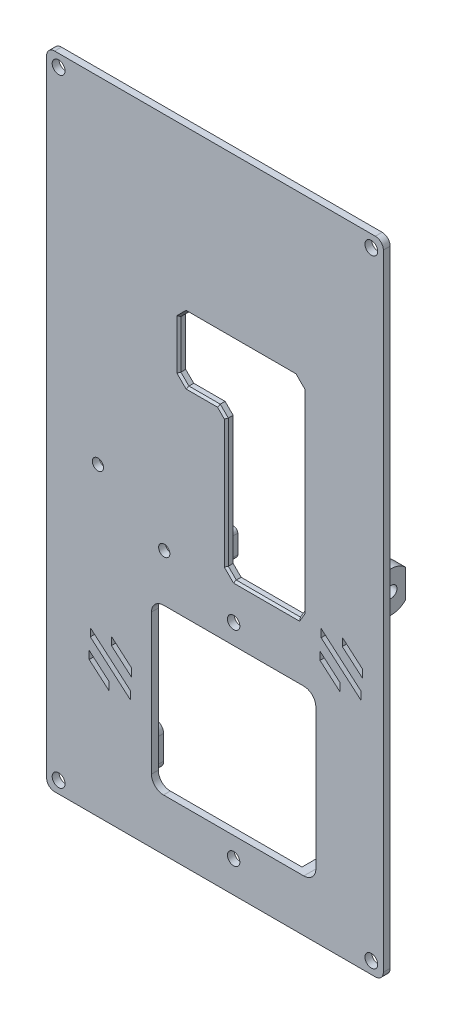
SolidWorks part; units mm, degrees
ref_plane "前视基准面" through (0, 0, 0) normal (0, 0, 1) x (1, 0, 0)
ref_plane "上视基准面" through (0, 0, 0) normal (0, 1, 0) x (1, 0, 0)
ref_plane "右视基准面" through (0, 0, 0) normal (1, 0, 0) x (0, 0, -1)
sketch "草图1" plane through (0, 0, 0) normal (0, 0, 1) x (1, 0, 0)
  line L0 (-263.3587, 1400.9403) -> (-185.3587, 1400.9403) construction
  line L17 (-203.4669, 1467.4701) -> (-189.703, 1467.4701)
  line L18 (-205.2557, 1468.5757) -> (-214.1502, 1486.3645)
  line L19 (-237.1098, 1489.3645) -> (-241.3399, 1480.9044)
  line L20 (-241.9491, 1480.1837) -> (-254.721, 1470.855)
  line L21 (-255.9007, 1470.4701) -> (-262.703, 1470.4701)
  line L22 (-266.703, 1466.4701) -> (-266.703, 1318.4701)
  line L23 (-262.703, 1314.4701) -> (-255.9007, 1314.4701)
  line L24 (-254.721, 1314.0852) -> (-241.9491, 1304.7565)
  line L25 (-241.3399, 1304.0358) -> (-237.1098, 1295.5757)
  line L26 (-235.321, 1294.4701) -> (-214.0849, 1294.4701)
  line L27 (-212.2961, 1295.5757) -> (-208.066, 1304.0358)
  line L28 (-207.4568, 1304.7565) -> (-194.6849, 1314.0852)
  line L29 (-193.5052, 1314.4701) -> (-186.703, 1314.4701)
  line L30 (-182.703, 1318.4701) -> (-182.703, 1466.4701)
  line L31 (-186.703, 1470.4701) -> (-193.5052, 1470.4701)
  line L32 (-194.6849, 1470.855) -> (-207.4568, 1480.1837)
  line L33 (-208.066, 1480.9044) -> (-212.2961, 1489.3645)
  line L34 (-214.0849, 1490.4701) -> (-235.321, 1490.4701)
  line L35 (-233.4669, 1487.4701) -> (-215.939, 1487.4701)
  line L36 (-235.2557, 1486.3645) -> (-244.1502, 1468.5757)
  line L37 (-245.939, 1467.4701) -> (-259.703, 1467.4701)
  line L38 (-263.703, 1321.4701) -> (-263.703, 1463.4701)
  line L39 (-263.703, 1321.4701) -> (-263.703, 1328.4701)
  line L40 (-259.703, 1317.4701) -> (-245.939, 1317.4701)
  line L41 (-244.1502, 1316.3645) -> (-235.2557, 1298.5757)
  line L42 (-233.4669, 1297.4701) -> (-215.939, 1297.4701)
  line L43 (-214.1502, 1298.5757) -> (-205.2557, 1316.3645)
  line L44 (-185.703, 1321.4701) -> (-185.703, 1463.4701)
  line L45 (-203.4669, 1317.4701) -> (-189.703, 1317.4701)
  circle A20 centre (-201.703, 1470.9701) radius 1.6
  circle A21 centre (-247.703, 1470.9701) radius 1.6
  circle A22 centre (-247.703, 1313.9701) radius 1.6
  circle A23 centre (-201.703, 1313.9701) radius 1.6
  arc A24 (-241.9491, 1480.1837) -> (-241.3399, 1480.9044) centre (-243.1288, 1481.7988) ccw
  arc A25 (-255.9007, 1470.4701) -> (-254.721, 1470.855) centre (-255.9007, 1472.4701) ccw
  arc A26 (-262.703, 1470.4701) -> (-266.703, 1466.4701) centre (-262.703, 1466.4701) ccw
  arc A27 (-266.703, 1318.4701) -> (-262.703, 1314.4701) centre (-262.703, 1318.4701) ccw
  arc A28 (-254.721, 1314.0852) -> (-255.9007, 1314.4701) centre (-255.9007, 1312.4701) ccw
  arc A29 (-241.3399, 1304.0358) -> (-241.9491, 1304.7565) centre (-243.1288, 1303.1414) ccw
  arc A30 (-237.1098, 1295.5757) -> (-235.321, 1294.4701) centre (-235.321, 1296.4701) ccw
  arc A31 (-214.0849, 1294.4701) -> (-212.2961, 1295.5757) centre (-214.0849, 1296.4701) ccw
  arc A32 (-207.4568, 1304.7565) -> (-208.066, 1304.0358) centre (-206.2771, 1303.1414) ccw
  arc A33 (-193.5052, 1314.4701) -> (-194.6849, 1314.0852) centre (-193.5052, 1312.4701) ccw
  arc A34 (-186.703, 1314.4701) -> (-182.703, 1318.4701) centre (-186.703, 1318.4701) ccw
  arc A35 (-182.703, 1466.4701) -> (-186.703, 1470.4701) centre (-186.703, 1466.4701) ccw
  arc A36 (-194.6849, 1470.855) -> (-193.5052, 1470.4701) centre (-193.5052, 1472.4701) ccw
  arc A37 (-208.066, 1480.9044) -> (-207.4568, 1480.1837) centre (-206.2771, 1481.7988) ccw
  arc A38 (-212.2961, 1489.3645) -> (-214.0849, 1490.4701) centre (-214.0849, 1488.4701) ccw
  arc A39 (-235.321, 1490.4701) -> (-237.1098, 1489.3645) centre (-235.321, 1488.4701) ccw
  arc A40 (-185.703, 1463.4701) -> (-189.703, 1467.4701) centre (-189.703, 1463.4701) ccw
  arc A41 (-205.2557, 1468.5757) -> (-203.4669, 1467.4701) centre (-203.4669, 1469.4701) ccw
  arc A42 (-214.1502, 1486.3645) -> (-215.939, 1487.4701) centre (-215.939, 1485.4701) ccw
  arc A43 (-233.4669, 1487.4701) -> (-235.2557, 1486.3645) centre (-233.4669, 1485.4701) ccw
  arc A44 (-245.939, 1467.4701) -> (-244.1502, 1468.5757) centre (-245.939, 1469.4701) ccw
  arc A45 (-259.703, 1467.4701) -> (-263.703, 1463.4701) centre (-259.703, 1463.4701) ccw
  arc A46 (-263.703, 1321.4701) -> (-259.703, 1317.4701) centre (-259.703, 1321.4701) ccw
  arc A47 (-244.1502, 1316.3645) -> (-245.939, 1317.4701) centre (-245.939, 1315.4701) ccw
  arc A48 (-235.2557, 1298.5757) -> (-233.4669, 1297.4701) centre (-233.4669, 1299.4701) ccw
  arc A49 (-215.939, 1297.4701) -> (-214.1502, 1298.5757) centre (-215.939, 1299.4701) ccw
  arc A50 (-203.4669, 1317.4701) -> (-205.2557, 1316.3645) centre (-203.4669, 1315.4701) ccw
  arc A51 (-189.703, 1317.4701) -> (-185.703, 1321.4701) centre (-189.703, 1321.4701) ccw
  dimension "D2" = 3.2
  dimension "D3" = 3.2
  dimension "D4" = 3.2
  dimension "D5" = 3.2
  dimension "D1" = 78
extrude "凸台-拉伸2" add sketch "草图1" along normal blind 1.7 contours L34 A39 L19 A24 L20 A25 L21 A26 L22 A27 L23 A28 L24 A29 L25 A30 L26 A31 L27 A32 L28 A33 L29 A34 L30 A35 L31 A36 L32 A37 L33 A38 A51 L45 A50 L43 A49 L42 A48 L41 A47 L40 A46 L38 A45 L37 A44 L36 A43
sketch "草图2" plane through (0, 0, 0) normal (0, 0, -1) x (-1, 0, 0)
  line L0 (203.4669, 1467.4701) -> (189.703, 1467.4701) construction
  line L1 (205.2557, 1468.5757) -> (214.1502, 1486.3645) construction
  line L2 (233.4669, 1487.4701) -> (215.939, 1487.4701) construction
  line L3 (235.2557, 1486.3645) -> (244.1502, 1468.5757) construction
  line L4 (245.939, 1467.4701) -> (259.703, 1467.4701) construction
  line L5 (203.4669, 1467.4701) -> (189.703, 1467.4701)
  line L6 (205.2557, 1468.5757) -> (214.1502, 1486.3645)
  line L7 (233.4669, 1487.4701) -> (215.939, 1487.4701)
  line L8 (235.2557, 1486.3645) -> (244.1502, 1468.5757)
  line L9 (245.939, 1467.4701) -> (259.703, 1467.4701)
  line L10 (263.703, 1463.4701) -> (263.703, 1438.4701)
  line L11 (263.703, 1321.4701) -> (263.703, 1463.4701) construction
  line L12 (263.703, 1438.4701) -> (185.703, 1438.4701)
  line L13 (185.703, 1321.4701) -> (185.703, 1463.4701) construction
  line L14 (185.703, 1438.4701) -> (185.703, 1463.4701)
  line L15 (263.703, 1392.4701) -> (185.703, 1392.4701) construction
  line L16 (185.703, 1346.4701) -> (185.703, 1321.4701)
  line L17 (263.703, 1346.4701) -> (185.703, 1346.4701)
  line L18 (263.703, 1321.4701) -> (263.703, 1346.4701)
  line L19 (245.939, 1317.4701) -> (259.703, 1317.4701)
  line L20 (235.2557, 1298.5757) -> (244.1502, 1316.3645)
  line L21 (233.4669, 1297.4701) -> (215.939, 1297.4701)
  line L22 (205.2557, 1316.3645) -> (214.1502, 1298.5757)
  line L23 (203.4669, 1317.4701) -> (189.703, 1317.4701)
  arc A0 (189.703, 1467.4701) -> (185.703, 1463.4701) centre (189.703, 1463.4701) ccw construction
  arc A1 (203.4669, 1467.4701) -> (205.2557, 1468.5757) centre (203.4669, 1469.4701) ccw construction
  arc A2 (215.939, 1487.4701) -> (214.1502, 1486.3645) centre (215.939, 1485.4701) ccw construction
  arc A3 (235.2557, 1486.3645) -> (233.4669, 1487.4701) centre (233.4669, 1485.4701) ccw construction
  arc A4 (244.1502, 1468.5757) -> (245.939, 1467.4701) centre (245.939, 1469.4701) ccw construction
  arc A5 (263.703, 1463.4701) -> (259.703, 1467.4701) centre (259.703, 1463.4701) ccw construction
  arc A6 (189.703, 1467.4701) -> (185.703, 1463.4701) centre (189.703, 1463.4701) ccw
  arc A7 (203.4669, 1467.4701) -> (205.2557, 1468.5757) centre (203.4669, 1469.4701) ccw
  arc A8 (215.939, 1487.4701) -> (214.1502, 1486.3645) centre (215.939, 1485.4701) ccw
  arc A9 (235.2557, 1486.3645) -> (233.4669, 1487.4701) centre (233.4669, 1485.4701) ccw
  arc A10 (244.1502, 1468.5757) -> (245.939, 1467.4701) centre (245.939, 1469.4701) ccw
  arc A11 (263.703, 1463.4701) -> (259.703, 1467.4701) centre (259.703, 1463.4701) ccw
  arc A12 (263.703, 1321.4701) -> (259.703, 1317.4701) centre (259.703, 1321.4701) cw
  arc A13 (244.1502, 1316.3645) -> (245.939, 1317.4701) centre (245.939, 1315.4701) cw
  arc A14 (235.2557, 1298.5757) -> (233.4669, 1297.4701) centre (233.4669, 1299.4701) cw
  arc A15 (215.939, 1297.4701) -> (214.1502, 1298.5757) centre (215.939, 1299.4701) cw
  arc A16 (203.4669, 1317.4701) -> (205.2557, 1316.3645) centre (203.4669, 1315.4701) cw
  arc A17 (189.703, 1317.4701) -> (185.703, 1321.4701) centre (189.703, 1321.4701) cw
  dimension "D1" = 25
extrude "凸台-拉伸3" add sketch "草图2" against normal up to surface (1.7 mm away) up to face at (-224.703, 1392.4701, 1.7)
sketch "草图3" plane through (0, 0, 1.7) normal (0, 0, 1) x (1, 0, 0)
  line L0 (-185.703, 1321.4701) -> (-185.703, 1463.4701) construction
  line L1 (-263.703, 1346.4701) -> (-185.703, 1346.4701)
  line L2 (-263.703, 1346.4701) -> (-263.703, 1386.3195)
  line L4 (-185.703, 1346.4701) -> (-185.703, 1386.3195)
  line L5 (-185.703, 1438.4701) -> (-263.703, 1438.4701) construction
  line L6 (-185.703, 1438.4701) -> (-217.203, 1438.4701)
  line L7 (-185.703, 1438.4701) -> (-185.703, 1386.3195)
  line L9 (-217.203, 1438.4701) -> (-217.203, 1388.4701)
  line L10 (-217.203, 1388.4701) -> (-245.703, 1388.4701)
  line L12 (-263.703, 1386.3195) -> (-263.703, 1438.4701)
  line L13 (-263.703, 1438.4701) -> (-245.703, 1438.4701)
  line L14 (-245.703, 1388.4701) -> (-245.703, 1438.4701)
  dimension "D3" = 50
  dimension "D1" = 31.5
  dimension "D2" = 18
extrude "凸台-拉伸4" add sketch "草图3" against normal up to surface (1.7 mm away) up to face at (-224.703, 1392.4701, 0)
sketch "草图5" plane through (0, 0, 0) normal (0, 0, -1) x (-1, 0, 0)
  line L0 (182.703, 1392.4701) -> (266.703, 1392.4701) construction
  line L1 (182.703, 1318.4701) -> (182.703, 1466.4701) construction
  line L2 (266.703, 1466.4701) -> (266.703, 1318.4701) construction
  line L3 (224.703, 1490.4701) -> (224.703, 1294.4701) construction
  line L4 (214.0849, 1490.4701) -> (235.321, 1490.4701) construction
  line L5 (235.321, 1294.4701) -> (214.0849, 1294.4701) construction
  line L6 (194.703, 1333.4701) -> (204.703, 1323.4701) construction
  line L7 (196.703, 1461.4701) -> (202.703, 1461.4701)
  line L8 (194.703, 1459.4701) -> (194.703, 1453.4701)
  line L9 (196.703, 1451.4701) -> (202.703, 1451.4701)
  line L10 (204.703, 1459.4701) -> (204.703, 1453.4701)
  line L11 (194.703, 1461.4701) -> (204.703, 1451.4701) construction
  line L12 (194.703, 1451.4701) -> (204.703, 1461.4701) construction
  line L13 (194.703, 1323.4701) -> (204.703, 1333.4701) construction
  line L14 (204.703, 1325.4701) -> (204.703, 1331.4701)
  line L15 (196.703, 1333.4701) -> (202.703, 1333.4701)
  line L16 (194.703, 1325.4701) -> (194.703, 1331.4701)
  line L17 (196.703, 1323.4701) -> (202.703, 1323.4701)
  line L18 (254.703, 1323.4701) -> (244.703, 1333.4701) construction
  line L19 (254.703, 1451.4701) -> (244.703, 1461.4701) construction
  line L20 (254.703, 1461.4701) -> (244.703, 1451.4701) construction
  line L21 (254.703, 1333.4701) -> (244.703, 1323.4701) construction
  line L22 (252.703, 1323.4701) -> (246.703, 1323.4701)
  line L23 (254.703, 1325.4701) -> (254.703, 1331.4701)
  line L24 (252.703, 1333.4701) -> (246.703, 1333.4701)
  line L25 (244.703, 1325.4701) -> (244.703, 1331.4701)
  line L26 (244.703, 1459.4701) -> (244.703, 1453.4701)
  line L27 (252.703, 1451.4701) -> (246.703, 1451.4701)
  line L28 (254.703, 1459.4701) -> (254.703, 1453.4701)
  line L29 (252.703, 1461.4701) -> (246.703, 1461.4701)
  arc A0 (202.703, 1461.4701) -> (204.703, 1459.4701) centre (202.703, 1459.4701) cw
  arc A1 (202.703, 1451.4701) -> (204.703, 1453.4701) centre (202.703, 1453.4701) ccw
  arc A2 (194.703, 1453.4701) -> (196.703, 1451.4701) centre (196.703, 1453.4701) ccw
  arc A3 (196.703, 1461.4701) -> (194.703, 1459.4701) centre (196.703, 1459.4701) ccw
  arc A4 (196.703, 1323.4701) -> (194.703, 1325.4701) centre (196.703, 1325.4701) cw
  arc A5 (194.703, 1331.4701) -> (196.703, 1333.4701) centre (196.703, 1331.4701) cw
  arc A6 (202.703, 1333.4701) -> (204.703, 1331.4701) centre (202.703, 1331.4701) cw
  arc A7 (202.703, 1323.4701) -> (204.703, 1325.4701) centre (202.703, 1325.4701) ccw
  arc A8 (252.703, 1333.4701) -> (254.703, 1331.4701) centre (252.703, 1331.4701) cw
  arc A9 (254.703, 1325.4701) -> (252.703, 1323.4701) centre (252.703, 1325.4701) cw
  arc A10 (244.703, 1325.4701) -> (246.703, 1323.4701) centre (246.703, 1325.4701) ccw
  arc A11 (244.703, 1331.4701) -> (246.703, 1333.4701) centre (246.703, 1331.4701) cw
  arc A12 (246.703, 1451.4701) -> (244.703, 1453.4701) centre (246.703, 1453.4701) cw
  arc A13 (254.703, 1453.4701) -> (252.703, 1451.4701) centre (252.703, 1453.4701) cw
  arc A14 (252.703, 1461.4701) -> (254.703, 1459.4701) centre (252.703, 1459.4701) cw
  arc A15 (246.703, 1461.4701) -> (244.703, 1459.4701) centre (246.703, 1459.4701) ccw
  point P12 (199.703, 1456.4701)
  point P21 (199.703, 1328.4701)
  point P30 (249.703, 1328.4701)
  point P31 (249.703, 1456.4701)
  dimension "D5" = 2
  dimension "D6" = 2
  dimension "D1" = 10
  dimension "D2" = 10
  dimension "D3" = 25
  dimension "D4" = 64
extrude "凸台-拉伸5" add sketch "草图5" along normal blind 5.5
sketch "草图7" plane through (0, 0, 1.7) normal (0, 0, 1) x (1, 0, 0)
  line L1 (-217.203, 1438.4701) -> (-227.7886, 1438.4701)
  line L2 (-217.203, 1438.4701) -> (-217.203, 1401.7435)
  line L3 (-217.203, 1401.7435) -> (-227.7886, 1401.7435)
  line L4 (-227.7886, 1438.4701) -> (-227.7886, 1401.7435)
extrude "凸台-拉伸7" add sketch "草图7" against normal up to surface (1.7 mm away) up to face at (-249.703, 1328.4701, 0)
chamfer "倒角1" distance 2 angle 45 5 edges at (-245.703, 1388.4701, 0.85) (-245.703, 1438.4701, 0.85) (-227.7886, 1438.4701, 0.85) (-227.7886, 1401.7435, 0.85) (-217.203, 1388.4701, 0.85)
sketch "草图8" plane through (0, 0, 1.7) normal (0, 0, 1) x (1, 0, 0)
  line L0 (-237.3567, 1378.2457) -> (-253.8936, 1388.5791) construction
  line L1 (-253.8936, 1388.5791) -> (-253.8936, 1375.7571) construction
  line L2 (-266.703, 1466.4701) -> (-266.703, 1318.4701) construction
  circle A0 centre (-237.3567, 1378.2457) radius 1.4
  circle A1 centre (-253.8936, 1388.5791) radius 1.4
  dimension "D1" = 19.5
  dimension "D2" = 58
extrude "切除-拉伸2" cut sketch "草图8" against normal up to surface (1.7 mm away) up to face at (-231.2341, 1410.4537, 0)
sketch "草图9" plane through (0, 0, 0) normal (0, 0, -1) x (-1, 0, 0)
  line L0 (245.703, 1395.2979) -> (247.703, 1395.2979)
  line L1 (245.703, 1390.4701) -> (245.703, 1436.4701) construction
  line L2 (248.703, 1394.2979) -> (248.703, 1385.8752)
  line L3 (248.203, 1385.0092) -> (242.935, 1381.9678)
  line L4 (242.435, 1381.8338) -> (223.703, 1381.8338)
  line L5 (222.703, 1382.8338) -> (222.703, 1387.4701)
  line L6 (223.703, 1388.4701) -> (243.703, 1388.4701)
  line L7 (245.703, 1390.4701) -> (245.703, 1395.2979)
  line L8 (219.203, 1388.4701) -> (243.703, 1388.4701) construction
  line L9 (245.703, 1390.4701) -> (243.703, 1388.4701) construction
  line L10 (245.703, 1390.4701) -> (243.703, 1388.4701)
  arc A0 (222.703, 1387.4701) -> (223.703, 1388.4701) centre (223.703, 1387.4701) cw
  arc A1 (223.703, 1381.8338) -> (222.703, 1382.8338) centre (223.703, 1382.8338) cw
  arc A2 (242.935, 1381.9678) -> (242.435, 1381.8338) centre (242.435, 1382.8338) cw
  arc A3 (248.703, 1385.8752) -> (248.203, 1385.0092) centre (247.703, 1385.8752) cw
  arc A4 (247.703, 1395.2979) -> (248.703, 1394.2979) centre (247.703, 1394.2979) cw
  point P16 (222.703, 1381.8338)
  point P19 (242.703, 1381.8338)
  point P22 (248.703, 1385.2979)
  point P25 (248.703, 1395.2979)
  dimension "D6" = 1
  dimension "D1" = 3
  dimension "D2" = 10
  dimension "D3" = 120
  dimension "D4" = 6
  dimension "D5" = 20
extrude "凸台-拉伸8" add sketch "草图9" along normal blind 2
sketch "草图10" plane through (0, 0, 1.7) normal (0, 0, 1) x (1, 0, 0)
  line L0 (-266.703, 1466.4701) -> (-266.703, 1318.4701) construction
  line L1 (-228.703, 1332.4701) -> (-220.703, 1332.4701)
  line L2 (-229.703, 1333.4701) -> (-229.703, 1341.4701)
  line L3 (-228.703, 1342.4701) -> (-220.703, 1342.4701)
  line L4 (-219.703, 1333.4701) -> (-219.703, 1341.4701)
  line L5 (-235.321, 1294.4701) -> (-214.0849, 1294.4701) construction
  arc A0 (-220.703, 1342.4701) -> (-219.703, 1341.4701) centre (-220.703, 1341.4701) cw
  arc A1 (-220.703, 1332.4701) -> (-219.703, 1333.4701) centre (-220.703, 1333.4701) ccw
  arc A2 (-228.703, 1332.4701) -> (-229.703, 1333.4701) centre (-228.703, 1333.4701) cw
  arc A3 (-229.703, 1341.4701) -> (-228.703, 1342.4701) centre (-228.703, 1341.4701) cw
  point P10 (-219.703, 1342.4701)
  point P13 (-219.703, 1332.4701)
  point P16 (-229.703, 1332.4701)
  dimension "D5" = 1
  dimension "D1" = 37
  dimension "D2" = 10
  dimension "D3" = 10
  dimension "D4" = 38
extrude "切除-拉伸3" cut sketch "草图10" against normal up to surface (1.7 mm away) up to face at (-249.703, 1456.4701, 0)
sketch "草图11" plane through (-266.703, 0, 0) normal (-1, 0, 0) x (0, 0, 1)
  line L0 (0, 1321.4701) -> (0, 1463.4701) construction
  line L1 (-3.5, 1392.4701) -> (0, 1392.4701) construction
  line L2 (-3.5, 1392.4701) -> (0, 1392.4701) construction
  line L3 (-3.5, 1397.4701) -> (0, 1397.4701)
  line L4 (-3.5, 1387.4701) -> (0, 1387.4701)
  line L5 (0, 1387.4701) -> (0, 1397.4701)
  line L6 (2.0483, 1392.4701) -> (7.0966, 1392.4701) construction
  line L7 (-7, 1388.8994) -> (-7, 1396.0408)
  circle A0 centre (-3.5, 1392.4701) radius 1.4
  arc A1 (-3.5, 1397.4701) -> (-7, 1396.0408) centre (-3.5, 1392.4701) ccw
  arc A2 (-7, 1388.8994) -> (-3.5, 1387.4701) centre (-3.5, 1392.4701) ccw
  point P4 (0, 1392.4701)
  point P5 (-0.4759, 1392.4701)
  dimension "D1" = 2.8
  dimension "D2" = 3.5
  dimension "D4" = 3.5
  dimension "D3" = 10
extrude "凸台-拉伸9" add sketch "草图11" against normal blind 6.5
ref_plane "基准面1" through (-224.703, 0, 0) normal (1, 0, 0) x (0, 0, -1)
mirror "镜向1" about plane through (-224.703, 0, 0) normal (1, 0, 0) of "凸台-拉伸9"
fillet "圆角1" radius 2 4 edges at (-185.953, 1397.4701, 0) (-185.953, 1387.4701, 0) (-263.453, 1397.4701, 0) (-263.453, 1387.4701, 0)
sketch "草图12" plane through (0, 0, 0) normal (0, 0, -1) x (-1, 0, 0)
  line L0 (182.703, 1318.4701) -> (182.703, 1466.4701) construction
  line L1 (182.703, 1365.3922) -> (185.903, 1365.3922)
  line L2 (182.703, 1365.3922) -> (182.703, 1421.7692)
  line L3 (182.703, 1421.7692) -> (185.903, 1421.7692)
  line L4 (185.903, 1365.3922) -> (185.903, 1421.7692)
  line L5 (224.703, 1294.4701) -> (224.703, 1490.4701) construction
  line L6 (235.321, 1294.4701) -> (214.0849, 1294.4701) construction
  line L7 (214.0849, 1490.4701) -> (235.321, 1490.4701) construction
  line L8 (263.503, 1365.3922) -> (263.503, 1421.7692)
  line L9 (266.703, 1421.7692) -> (263.503, 1421.7692)
  line L10 (266.703, 1365.3922) -> (266.703, 1421.7692)
  line L11 (266.703, 1365.3922) -> (263.503, 1365.3922)
  dimension "D1" = 3.2
extrude "切除-拉伸4" cut sketch "草图12" along normal blind 10
fillet "圆角2" radius 2 2 edges at (-189.203, 1392.4701, 0) (-260.203, 1392.4701, 0)
sketch "草图13" plane through (0, 0, 1.7) normal (0, 0, 1) x (1, 0, 0)
  line L0 (-220.0468, 1320.3564) -> (-220.0468, 1371.3564) construction
  line L2 (-237.5468, 1325.3564) -> (-202.5468, 1325.3564)
  line L3 (-240.5468, 1328.3564) -> (-240.5468, 1363.3564)
  line L4 (-237.5468, 1366.3564) -> (-202.5468, 1366.3564)
  line L5 (-199.5468, 1328.3564) -> (-199.5468, 1363.3564)
  arc A0 (-237.5468, 1325.3564) -> (-240.5468, 1328.3564) centre (-237.5468, 1328.3564) cw
  arc A1 (-240.5468, 1363.3564) -> (-237.5468, 1366.3564) centre (-237.5468, 1363.3564) cw
  arc A2 (-202.5468, 1366.3564) -> (-199.5468, 1363.3564) centre (-202.5468, 1363.3564) cw
  arc A3 (-202.5468, 1325.3564) -> (-199.5468, 1328.3564) centre (-202.5468, 1328.3564) ccw
  circle A4 centre (-220.0468, 1320.3564) radius 1.55
  circle A5 centre (-220.0468, 1371.3564) radius 1.55
  point P6 (-220.0468, 1345.8564)
  point P7 (-199.5468, 1345.8564)
  point P8 (-220.0468, 1325.3564)
  point P11 (-240.5468, 1325.3564)
  point P16 (-199.5468, 1366.3564)
  point P19 (-199.5468, 1325.3564)
  dimension "D4" = 3
  dimension "D5" = 3.1
  dimension "D6" = 3.1
  dimension "D1" = 51
  dimension "D2" = 41
  dimension "D3" = 41
extrude "切除-拉伸5" cut sketch "草图13" against normal blind 10
fillet "圆角3" radius 3 1 edges at (-199.5468, 1333.4701, -2.75)
sketch "草图14" plane through (0, 0, 1.7) normal (0, 0, 1) x (1, 0, 0)
  line L0 (-256.0899, 1347.3425) -> (-251.0899, 1343.0415) construction
  line L1 (-255.8105, 1352.3784) -> (-245.8105, 1343.7765) construction
  line L2 (-250.5311, 1353.1133) -> (-245.5311, 1348.8124) construction
  line L3 (-253.5899, 1345.192) -> (-248.0311, 1350.9628) construction
  line L8 (-245.5311, 1346.8124) -> (-245.5311, 1348.8124)
  line L9 (-245.5311, 1346.8124) -> (-250.5311, 1351.1133)
  line L10 (-245.5311, 1348.8124) -> (-250.5311, 1353.1133)
  line L11 (-250.5311, 1351.1133) -> (-250.5311, 1353.1133)
  line L12 (-245.8105, 1341.7765) -> (-245.8105, 1343.7765)
  line L13 (-245.8105, 1341.7765) -> (-255.8105, 1350.3784)
  line L14 (-245.8105, 1343.7765) -> (-255.8105, 1352.3784)
  line L15 (-255.8105, 1350.3784) -> (-255.8105, 1352.3784)
  line L16 (-251.0899, 1341.0415) -> (-251.0899, 1343.0415)
  line L17 (-251.0899, 1341.0415) -> (-256.0899, 1345.3425)
  line L18 (-251.0899, 1343.0415) -> (-256.0899, 1347.3425)
  line L19 (-256.0899, 1345.3425) -> (-256.0899, 1347.3425)
  line L20 (-198.508, 1375.9434) -> (-193.508, 1371.6425) construction
  line L21 (-198.2286, 1380.9793) -> (-188.2286, 1372.3774) construction
  line L22 (-192.9492, 1381.7143) -> (-187.9492, 1377.4133) construction
  line L23 (-196.008, 1373.793) -> (-190.4492, 1379.5638) construction
  line L24 (-187.9492, 1375.4133) -> (-187.9492, 1377.4133)
  line L25 (-187.9492, 1375.4133) -> (-192.9492, 1379.7143)
  line L26 (-187.9492, 1377.4133) -> (-192.9492, 1381.7143)
  line L27 (-192.9492, 1379.7143) -> (-192.9492, 1381.7143)
  line L28 (-188.2286, 1370.3774) -> (-188.2286, 1372.3774)
  line L29 (-188.2286, 1370.3774) -> (-198.2286, 1378.9793)
  line L30 (-188.2286, 1372.3774) -> (-198.2286, 1380.9793)
  line L31 (-198.2286, 1378.9793) -> (-198.2286, 1380.9793)
  line L32 (-193.508, 1369.6425) -> (-193.508, 1371.6425)
  line L33 (-193.508, 1369.6425) -> (-198.508, 1373.9434)
  line L34 (-193.508, 1371.6425) -> (-198.508, 1375.9434)
  line L35 (-198.508, 1373.9434) -> (-198.508, 1375.9434)
  point P8 (-250.8105, 1348.0774)
  point P23 (-193.2286, 1376.6784)
  dimension "D1" = 5
  dimension "D2" = 5
  dimension "D3" = 10
  dimension "D4" = 4
  dimension "D5" = 4
  dimension "D6" = 2
  dimension "D7" = 2
  dimension "D8" = 2
  dimension "D9" = 5
  dimension "D10" = 10
  dimension "D11" = 4
  dimension "D12" = 4
  dimension "D13" = 5
  dimension "D14" = 2
  dimension "D15" = 2
  dimension "D16" = 2
extrude "切除-拉伸6" cut sketch "草图14" against normal up to surface (1.7 mm away) up to face at (-218.4968, 1371.3564, 0)
sketch "草图16" plane through (0, 0, 1.7) normal (0, 0, 1) x (1, 0, 0)
  line L0 (-229.7886, 1438.4701) -> (-227.7886, 1436.4701) construction
  line L1 (-227.7886, 1436.4701) -> (-227.7886, 1403.7435) construction
  line L2 (-227.7886, 1403.7435) -> (-225.7886, 1401.7435) construction
  line L3 (-225.7886, 1401.7435) -> (-217.203, 1401.7435) construction
  line L4 (-217.203, 1401.7435) -> (-217.203, 1390.4701) construction
  line L5 (-217.203, 1390.4701) -> (-219.203, 1388.4701) construction
  line L6 (-219.203, 1388.4701) -> (-243.703, 1388.4701) construction
  line L7 (-243.703, 1388.4701) -> (-245.703, 1390.4701) construction
  line L8 (-245.703, 1390.4701) -> (-245.703, 1436.4701) construction
  line L9 (-245.703, 1436.4701) -> (-243.703, 1438.4701) construction
  line L10 (-229.7886, 1438.4701) -> (-243.703, 1438.4701) construction
  line L11 (-229.7886, 1438.4701) -> (-227.7886, 1436.4701)
  line L12 (-227.7886, 1436.4701) -> (-227.7886, 1403.7435)
  line L13 (-227.7886, 1403.7435) -> (-225.7886, 1401.7435)
  line L14 (-225.7886, 1401.7435) -> (-217.203, 1401.7435)
  line L15 (-217.203, 1401.7435) -> (-217.203, 1390.4701)
  line L16 (-217.203, 1390.4701) -> (-219.203, 1388.4701)
  line L17 (-219.203, 1388.4701) -> (-243.703, 1388.4701)
  line L18 (-243.703, 1388.4701) -> (-245.703, 1390.4701)
  line L19 (-245.703, 1390.4701) -> (-245.703, 1436.4701)
  line L20 (-245.703, 1436.4701) -> (-243.703, 1438.4701)
  line L21 (-229.7886, 1438.4701) -> (-243.703, 1438.4701)
extrude "凸台-拉伸10" add sketch "草图16" against normal up to surface (1.7 mm away) up to face at (-248.0311, 1349.9628, 0)
sketch "草图15" plane through (0, 0, 0) normal (0, 0, -1) x (-1, 0, 0)
  line L0 (202.5468, 1366.3564) -> (237.5468, 1366.3564) construction
  line L3 (182.703, 1318.4701) -> (182.703, 1466.4701) construction
  line L5 (223.703, 1428.3967) -> (223.703, 1381.8338) construction
  line L7 (202.703, 1430.3564) -> (204.703, 1432.3564)
  line L8 (231.703, 1416.3564) -> (233.703, 1418.3564)
  line L9 (203.8749, 1380.3564) -> (219.8749, 1380.3564)
  line L10 (202.703, 1382.3564) -> (202.703, 1430.3564)
  line L11 (204.703, 1432.3564) -> (222.703, 1432.3564)
  line L12 (221.8749, 1382.3564) -> (221.8749, 1414.3564)
  line L13 (231.703, 1432.3564) -> (233.703, 1430.3564)
  line L14 (222.703, 1432.3564) -> (231.703, 1432.3564)
  line L16 (223.8749, 1416.3564) -> (231.703, 1416.3564)
  line L17 (233.703, 1430.3564) -> (233.703, 1418.3564)
  line L18 (221.8749, 1414.3564) -> (223.8749, 1416.3564)
  line L19 (202.703, 1382.3564) -> (203.8749, 1380.3564)
  line L20 (219.8749, 1380.3564) -> (221.8749, 1382.3564)
  point P8 (233.703, 1416.3564)
  point P12 (221.8749, 1416.3564)
  point P14 (202.703, 1432.3564)
  point P15 (221.8749, 1380.3564)
  point P16 (233.703, 1432.3564)
  dimension "D2" = 14
  dimension "D3" = 31
  dimension "D4" = 16
  dimension "D5" = 20
extrude "切除-拉伸7" cut sketch "草图15" against normal blind 10
chamfer "倒角2" distance 0.5 angle 45 12 edges at (-202.703, 1406.3564, 1.7) (-203.703, 1431.3564, 1.7) (-218.203, 1432.3564, 1.7) (-232.703, 1431.3564, 1.7) (-233.703, 1424.3564, 1.7) (-232.703, 1417.3564, 1.7) (-227.7889, 1416.3564, 1.7) (-222.8749, 1415.3564, 1.7) (-221.8749, 1398.3564, 1.7) (-220.8749, 1381.3564, 1.7) (-211.8749, 1380.3564, 1.7) (-203.2889, 1381.3564, 1.7)
sketch "草图17" plane through (0, 0, 1.7) normal (0, 0, 1) x (1, 0, 0)
  circle A0 centre (-247.703, 1470.9701) radius 1.6 construction
  circle A1 centre (-201.703, 1470.9701) radius 1.6 construction
  circle A2 centre (-201.703, 1313.9701) radius 1.6 construction
  circle A3 centre (-247.703, 1313.9701) radius 1.6 construction
  circle A4 centre (-247.703, 1470.9701) radius 1.6
  circle A5 centre (-201.703, 1470.9701) radius 1.6
  circle A6 centre (-201.703, 1313.9701) radius 1.6
  circle A7 centre (-247.703, 1313.9701) radius 1.6
extrude "凸台-拉伸11" add sketch "草图17" against normal up to surface (1.7 mm away) up to face at (-219.3579, 1409.6897, 0)
sketch "草图18" plane through (0, 0, 1.7) normal (0, 0, 1) x (1, 0, 0)
  line L8 (-262.703, 1314.4701) -> (-186.703, 1314.4701)
  line L9 (-186.703, 1314.4701) -> (-186.703, 1288.2285)
  line L10 (-186.703, 1288.2285) -> (-262.703, 1288.2285)
  line L11 (-262.703, 1288.2285) -> (-262.703, 1314.4701)
  line L12 (-262.703, 1470.4701) -> (-186.703, 1470.4701)
  line L13 (-186.703, 1470.4701) -> (-186.703, 1499.8976)
  line L14 (-186.703, 1499.8976) -> (-262.703, 1499.8976)
  line L15 (-262.703, 1499.8976) -> (-262.703, 1470.4701)
extrude "切除-拉伸8" cut sketch "草图18" against normal up to surface (1.7 mm away) up to face at (-219.3579, 1409.6897, 0)
sketch "草图19" plane through (0, 0, 1.7) normal (0, 0, 1) x (1, 0, 0)
  line L0 (-266.703, 1326.3203) -> (-266.703, 1312.4701)
  line L1 (-266.703, 1466.4701) -> (-266.703, 1318.4701) construction
  line L2 (-266.703, 1312.4701) -> (-182.703, 1312.4701)
  line L3 (-182.703, 1312.4701) -> (-182.703, 1327.6302)
  line L4 (-182.703, 1318.4701) -> (-182.703, 1466.4701) construction
  line L5 (-182.703, 1327.6302) -> (-189.2539, 1327.6302)
  line L6 (-189.2539, 1327.6302) -> (-189.2539, 1314.4701)
  line L7 (-262.703, 1314.4701) -> (-186.703, 1314.4701) construction
  line L8 (-189.2539, 1314.4701) -> (-260.152, 1314.4701)
  line L9 (-260.152, 1314.4701) -> (-260.152, 1326.3203)
  line L10 (-260.152, 1326.3203) -> (-266.703, 1326.3203)
  line L11 (-266.703, 1392.4701) -> (-182.703, 1392.4701) construction
  line L12 (-260.152, 1470.4701) -> (-260.152, 1458.6199)
  line L13 (-189.2539, 1470.4701) -> (-260.152, 1470.4701)
  line L14 (-189.2539, 1457.31) -> (-189.2539, 1470.4701)
  line L15 (-182.703, 1457.31) -> (-189.2539, 1457.31)
  line L16 (-182.703, 1472.4701) -> (-182.703, 1457.31)
  line L17 (-266.703, 1472.4701) -> (-182.703, 1472.4701)
  line L18 (-266.703, 1458.6199) -> (-266.703, 1472.4701)
  line L19 (-260.152, 1458.6199) -> (-266.703, 1458.6199)
  dimension "D1" = 2
extrude "凸台-拉伸12" add sketch "草图19" against normal up to surface (1.7 mm away) up to face at (-219.3579, 1409.6897, 0)
sketch "草图20" plane through (0, 0, 1.7) normal (0, 0, 1) x (1, 0, 0)
  line L0 (-266.703, 1312.4701) -> (-182.703, 1312.4701) construction
  line L1 (-266.703, 1472.4701) -> (-266.703, 1312.4701) construction
  line L2 (-266.703, 1392.4701) -> (-182.703, 1392.4701) construction
  line L3 (-182.703, 1312.4701) -> (-182.703, 1472.4701) construction
  line L4 (-224.703, 1312.4701) -> (-224.703, 1472.4701) construction
  line L5 (-182.703, 1472.4701) -> (-266.703, 1472.4701) construction
  circle A0 centre (-263.703, 1315.4701) radius 1.6
  circle A1 centre (-263.703, 1469.4701) radius 1.6
  circle A2 centre (-185.703, 1315.4701) radius 1.6
  circle A3 centre (-185.703, 1469.4701) radius 1.6
  dimension "D1" = 3
  dimension "D2" = 3
extrude "切除-拉伸9" cut sketch "草图20" against normal up to surface (1.7 mm away) up to face at (-224.703, 1392.4701, 0)
fillet "圆角4" radius 2 4 edges at (-182.703, 1472.4701, 0.85) (-266.703, 1472.4701, 0.85) (-182.703, 1312.4701, 0.85) (-266.703, 1312.4701, 0.85)
